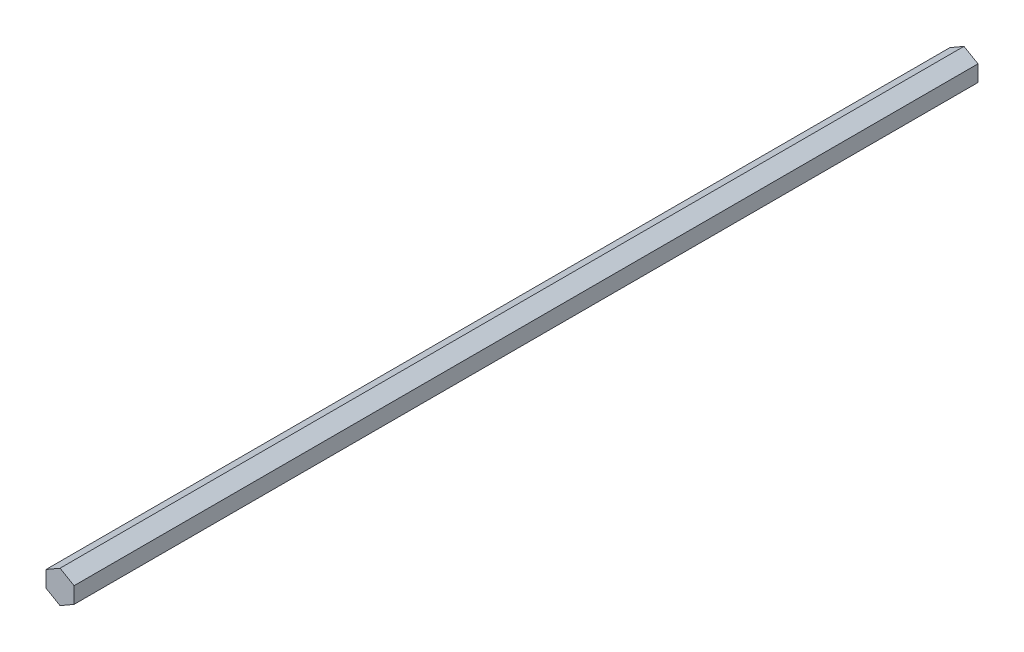
SolidWorks part; units mm, degrees
ref_plane "Front Plane" through (0, 0, 0) normal (0, 0, 1) x (1, 0, 0)
ref_plane "Top Plane" through (0, 0, 0) normal (0, 1, 0) x (1, 0, 0)
ref_plane "Right Plane" through (0, 0, 0) normal (1, 0, 0) x (0, 0, -1)
sketch "Sketch1" plane through (0, 0, 0) normal (0, 0, 1) x (1, 0, 0)
  line L1 (0, -7.3323) -> (6.35, -3.6662)
  line L2 (6.35, -3.6662) -> (6.35, 3.6662)
  line L3 (6.35, 3.6662) -> (0, 7.3323)
  line L4 (0, 7.3323) -> (-6.35, 3.6662)
  line L5 (-6.35, 3.6662) -> (-6.35, -3.6662)
  line L6 (-6.35, -3.6662) -> (0, -7.3323)
  circle A0 centre (0, 0) radius 6.35 construction
  dimension "D1" = 12.7
extrude "Boss-Extrude1" add sketch "Sketch1" along normal mid plane 408.94
